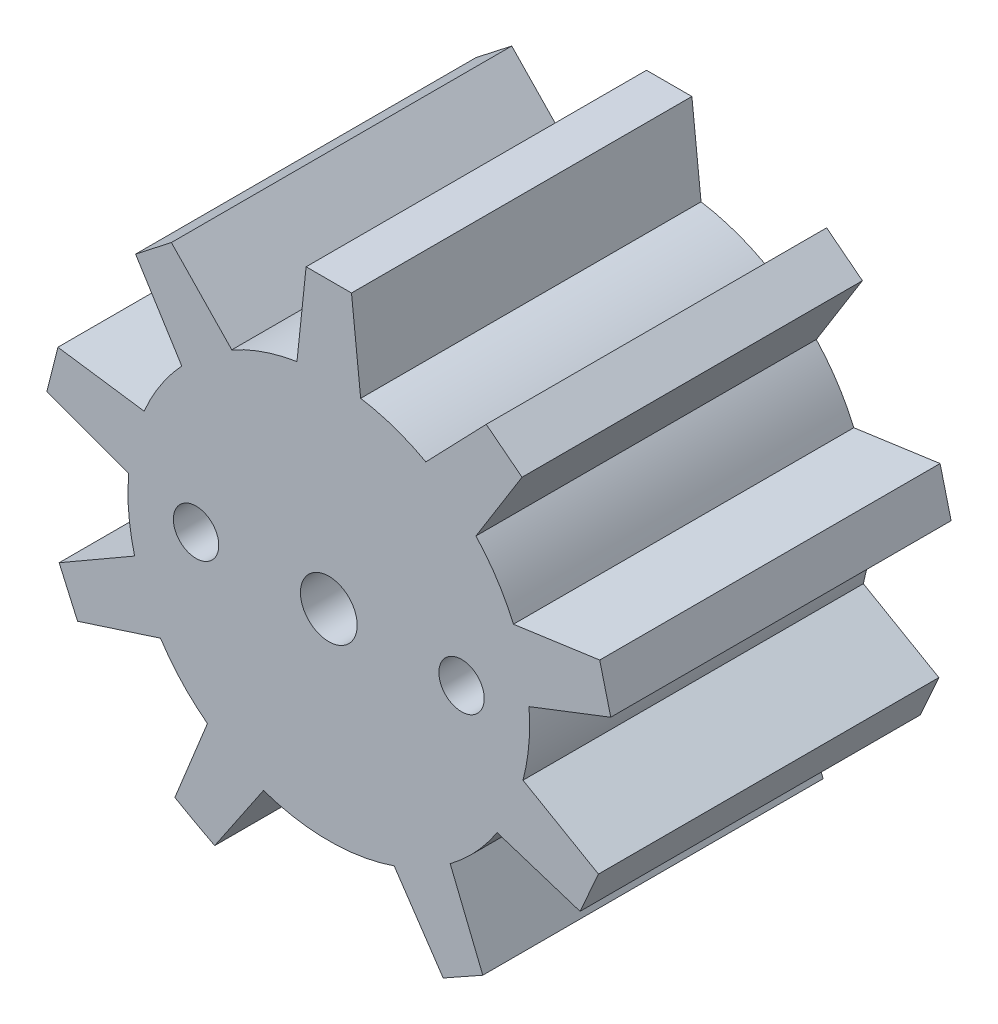
SolidWorks part; units mm, degrees
ref_plane "Спереди" through (0, 0, 0) normal (0, 0, 1) x (1, 0, 0)
ref_plane "Сверху" through (0, 0, 0) normal (0, 1, 0) x (1, 0, 0)
ref_plane "Справа" through (0, 0, 0) normal (1, 0, 0) x (0, 0, -1)
sketch "Эскиз3" plane through (0, 0, 0) normal (0, 0, 1) x (1, 0, 0)
  line B0 (0, 12.5567) -> (0, -11.4003) construction
  line B1 (-17.4471, 0) -> (17.8457, 0) construction
  line B2 (-1, 12.5567) -> (0, 12.5567)
  line B3 (0, 12.5567) -> (1, 12.5567)
  line B4 (-8.5148, 9.2827) -> (-6.9383, 10.5133)
  line B5 (-12.4239, 2.0778) -> (-11.9384, 4.018)
  line B6 (6.9383, 10.5133) -> (8.5148, 9.2827)
  line B7 (-11.883, -4.1789) -> (-11.0719, -6.007)
  line B8 (11.9384, 4.018) -> (12.4239, 2.0778)
  line B9 (11.0719, -6.007) -> (11.883, -4.1789)
  line B10 (-6.4791, 6.0286) -> (-8.5148, 9.2827)
  line B11 (-4.2757, 7.7486) -> (-6.9383, 10.5133)
  line B12 (-8.1384, 3.477) -> (-11.9384, 4.018)
  line B13 (-12.4239, 2.0778) -> (-8.8168, 0.7654)
  line B14 (-11.883, -4.1789) -> (-8.5563, -2.261)
  line B15 (-11.0719, -6.007) -> (-7.4176, -4.8272)
  line B16 (-1, 12.5567) -> (-1.4038, 8.738)
  line B17 (1, 12.5567) -> (1.4038, 8.738)
  line B18 (6.9383, 10.5133) -> (4.2757, 7.7486)
  line B19 (8.5148, 9.2827) -> (6.4833, 6.0241)
  line B20 (11.9384, 4.018) -> (8.1359, 3.4827)
  line B21 (12.4239, 2.0778) -> (8.8236, 0.6833)
  line B22 (11.883, -4.1789) -> (8.5563, -2.261)
  line B23 (11.0719, -6.007) -> (7.4176, -4.8272)
  arc B24 (-8.5563, -2.261) -> (-8.8168, 0.7654) centre (0, 0) cw
  arc B25 (-8.1384, 3.477) -> (-6.4791, 6.0286) centre (0, 0) cw
  arc B26 (-4.2757, 7.7486) -> (-1.4038, 8.738) centre (0, 0) cw
  arc B27 (1.4038, 8.738) -> (4.2757, 7.7486) centre (0, 0) cw
  arc B28 (6.4833, 6.0241) -> (8.1359, 3.4827) centre (0, 0) cw
  arc B29 (8.8236, 0.6833) -> (8.5563, -2.261) centre (0, 0) cw
  line B30 (-5.9113, -11.0782) -> (-6.7838, -10.5895)
  line B31 (-5.9113, -11.0782) -> (-5.0291, -11.549)
  line B32 (5.9134, -11.0771) -> (5.041, -11.5659)
  line B33 (2.8805, -8.3681) -> (5.041, -11.5659)
  line B34 (5.3502, -7.0497) -> (6.7858, -10.5883)
  line B35 (5.9134, -11.0771) -> (6.7858, -10.5883)
  line B36 (-6.7838, -10.5895) -> (-5.3488, -7.0507)
  line B37 (-2.879, -8.3686) -> (-5.0291, -11.549)
  arc B38 (-7.4176, -4.8272) -> (-5.3488, -7.0507) centre (0, 0) ccw
  arc B39 (-2.879, -8.3686) -> (2.8805, -8.3681) centre (0, 0) ccw
  arc B40 (5.3502, -7.0497) -> (7.4176, -4.8272) centre (0, 0) ccw
sketch_block_instance "Блок1-1"
sketch_block "Блок1" parameters "D1"=8.85
extrude "Бобышка-Вытянуть2" add sketch "Эскиз3" along normal blind 15
sketch "Эскиз5" plane through (0, 0, 0) normal (0, 0, -1) x (-1, 0, 0)
  circle A0 centre (0, 0) radius 1.25
extrude "Вырез-Вытянуть1" cut sketch "Эскиз5" against normal blind 15
sketch "Эскиз6" plane through (0, 0, 0) normal (0, 0, -1) x (-1, 0, 0)
  line L0 (0, 15.5561) -> (0, -12.7584) construction
  line L1 (16.6373, 0) -> (-21.3033, 0) construction
  circle A1 centre (5.85, 0) radius 1
  circle A4 centre (-5.85, 0) radius 1
extrude "Вырез-Вытянуть2" cut sketch "Эскиз6" against normal blind 29
